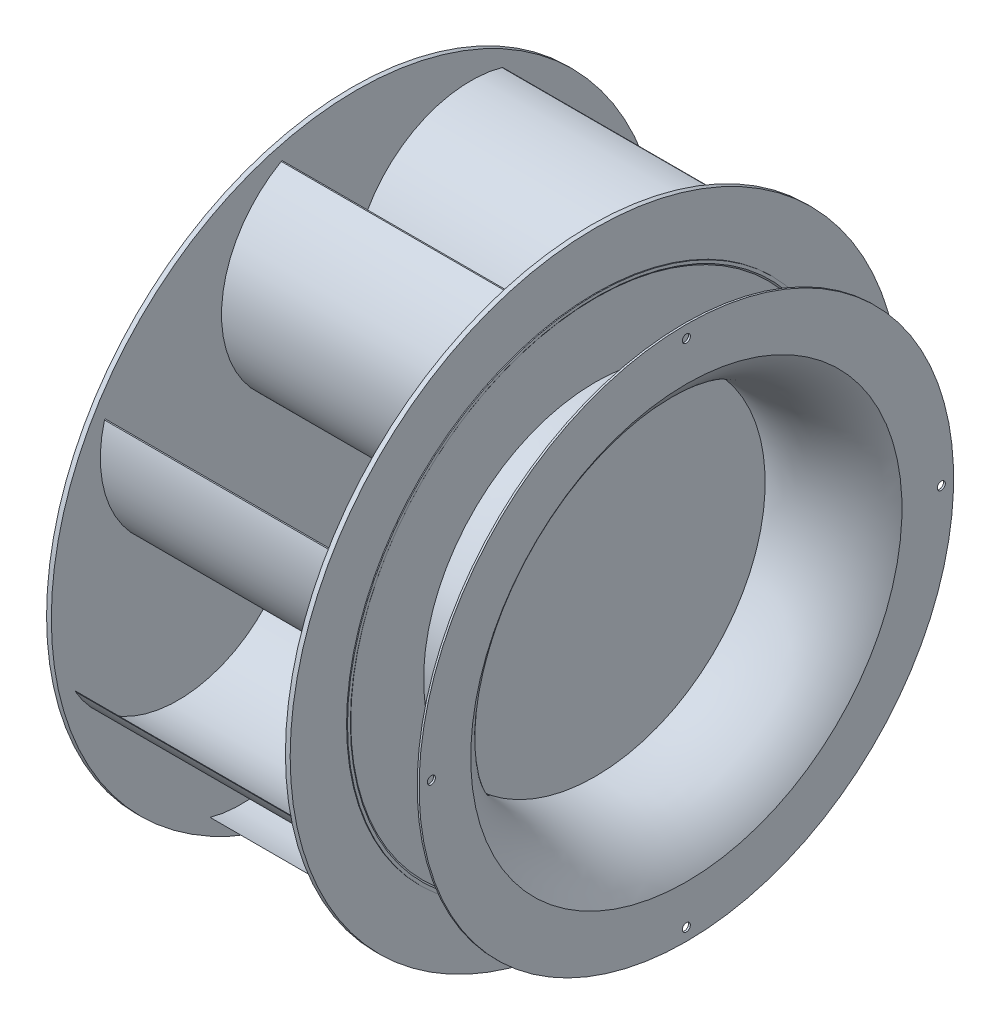
SolidWorks part; units mm, degrees
ref_plane "Front Plane" through (0, 0, 0) normal (0, 0, 1) x (1, 0, 0)
ref_plane "Top Plane" through (0, 0, 0) normal (0, 1, 0) x (1, 0, 0)
ref_plane "Right Plane" through (0, 0, 0) normal (1, 0, 0) x (0, 0, -1)
sketch "Sketch1" plane through (0, 0, 0) normal (0, 0, 1) x (1, 0, 0)
  line L0 (0, 0) -> (831.9083, 0) construction
  line L1 (0, 0) -> (0, 109)
  line L2 (5, 114) -> (70, 114)
  line L3 (70, 114) -> (70, 138)
  line L4 (70, 138) -> (90, 138)
  line L5 (90, 138) -> (90, 98)
  line L6 (90, 98) -> (95, 98)
  line L7 (95, 98) -> (95, 133)
  line L8 (95, 133) -> (105, 133)
  line L9 (105, 133) -> (105, 98)
  line L10 (105, 98) -> (129, 98)
  line L11 (129, 98) -> (129, 0)
  line L12 (129, 0) -> (0, 0)
  arc A0 (5, 114) -> (0, 109) centre (5, 109) ccw
  point P16 (0, 114)
  dimension "D10" = 5
  dimension "D1" = 114
  dimension "D2" = 24
  dimension "D3" = 70
  dimension "D4" = 40
  dimension "D5" = 35
  dimension "D6" = 5
  dimension "D7" = 20
  dimension "D8" = 10
  dimension "D9" = 59
revolve "Revolve1" add sketch "Sketch1" angle 360 about L0
sketch "Sketch2" plane through (129, 0, 0) normal (1, 0, 0) x (0, 0, -1)
  circle A0 centre (0, 0) radius 322
  dimension "D1" = 644
extrude "Extrude1" add sketch "Sketch2" along normal blind 5
sketch "Sketch9" plane through (129, 0, 0) normal (-1, 0, 0) x (0, 0, 1)
  circle A0 centre (0, 0) radius 317
  circle A1 centre (0, 0) radius 100
  circle A2 centre (0, 0) radius 322 construction
  dimension "D1" = 5
  dimension "D2" = 200
extrude "Extrude7" cut sketch "Sketch9" against normal blind 3
ref_plane "Plane1" through (381, 0, 0) normal (1, 0, 0) x (0, 0, -1)
sketch "Sketch3" plane through (381, 0, 0) normal (1, 0, 0) x (0, 0, -1)
  circle A0 centre (0, 0) radius 322
  dimension "D1" = 644
extrude "Extrude2" add sketch "Sketch3" along normal blind 5 separate body
sketch "Sketch4" plane through (134, 0, 0) normal (1, 0, 0) x (0, 0, -1)
  line L0 (0, 0) -> (0, 307) construction
  line L1 (0, 0) -> (161, 278.8602) construction
  line L2 (0, 112.5) -> (0.866, 112)
  line L3 (153.5, 265.8698) -> (154.366, 265.3698)
  circle A0 centre (0, 0) radius 307 construction
  circle A1 centre (0, 0) radius 322 construction
  circle A2 centre (0, 0) radius 112.5 construction
  arc A3 (0, 112.5) -> (153.5, 265.8698) centre (120.6282, 145.2694) cw
  arc A4 (0.866, 112) -> (154.366, 265.3698) centre (121.4942, 144.7694) cw
  dimension "D1" = 15
  dimension "D2" = 225
  dimension "D6" = 125
  dimension "D7" = 125
  dimension "D3" = 30
  dimension "D4" = 60
  dimension "D5" = 1
extrude "Extrude3" add sketch "Sketch4" along normal up to surface (252 mm away) up to face at (386, 0, -322)
ref_axis "Axis1" through (253.5503, 0, 0) along (-1, 0, 0)
pattern_circular "CirPattern1" count 8 over 360 about axis through (253.5503, 0, 0) along (-1, 0, 0) of "Extrude3"
sketch "Sketch5" plane through (0, 0, 0) normal (0, 0, 1) x (1, 0, 0)
  line L0 (0, 0) -> (527.2916, 0) construction
  line L1 (253.5503, 0) -> (75.411, 0) construction
  line L2 (386, 262.5) -> (387, 262.5)
  line L3 (387, 262.5) -> (387, 259.5)
  line L4 (386, 262.5) -> (386, 259.5)
  line L5 (384, 182.5) -> (384, 181.5)
  line L6 (70, 138) -> (70, -138) construction
  line L7 (386, -322) -> (386, 322) construction
  arc A0 (387, 259.5) -> (384, 182.5) centre (443.898, 218.7248) ccw
  arc A1 (386, 259.5) -> (384, 181.5) centre (443.1015, 219.0102) ccw
  dimension "D7" = 70
  dimension "D8" = 70
  dimension "D1" = 181.5
  dimension "D2" = 1
  dimension "D3" = 1
  dimension "D4" = 3
  dimension "D5" = 262.5
  dimension "D6" = 314
revolve "Revolve2" add sketch "Sketch5" angle 360 about L0
ref_plane "Plane3" through (482, 0, 0) normal (1, 0, 0) x (0, 0, -1)
sketch "Sketch6" plane through (0, 0, 0) normal (0, 0, 1) x (1, 0, 0)
  line L0 (482, 282) -> (480, 282)
  line L1 (482, -251.35) -> (482, 251.35) construction
  line L2 (480, 282) -> (480, 227.5)
  line L3 (0, 0) -> (615.1417, 0) construction
  line L4 (0, 114) -> (0, -114) construction
  line L5 (253.5503, 0) -> (75.411, 0) construction
  line L6 (482, 282) -> (482, 227.5)
  line L7 (378, 181.5) -> (382, 181.5)
  line L8 (378, 181.5) -> (378, 179.5)
  line L9 (378, 179.5) -> (382, 179.5)
  arc A0 (382, 181.5) -> (480, 227.5) centre (395.2724, 280.6153) ccw
  arc A1 (382, 179.5) -> (482, 227.5) centre (395.9922, 278.5163) ccw
  dimension "D7" = 100
  dimension "D8" = 100
  dimension "D1" = 282
  dimension "D2" = 2
  dimension "D3" = 227.5
  dimension "D4" = 104
  dimension "D5" = 181.5
  dimension "D6" = 4
revolve "Revolve3" add sketch "Sketch6" angle 360 about L3
sketch "Sketch7" plane through (482, 0, 0) normal (1, 0, 0) x (0, 0, -1)
  line L0 (0, 0) -> (0, 269) construction
  circle A0 centre (0, 0) radius 269 construction
  circle A1 centre (0, 269) radius 4.25
  dimension "D1" = 538
  dimension "D2" = 8.5
extrude "Extrude5" cut sketch "Sketch7" against normal blind 5
pattern_circular "CirPattern2" count 4 over 360 about axis through (253.5503, 0, 0) along (-1, 0, 0) of "Extrude5"
sketch "Sketch8" plane through (0, 0, 0) normal (1, 0, 0) x (0, 0, -1)
  line L0 (0, 0) -> (0, 126) construction
  circle A0 centre (0, 0) radius 126 construction
  circle A1 centre (0, 126) radius 5
  dimension "D1" = 252
  dimension "D2" = 10
extrude "Extrude6" cut sketch "Sketch8" along normal up to surface (90 mm away) up to face at (90, 0, 138)
pattern_circular "CirPattern3" count 8 over 360 about axis through (253.5503, 0, 0) along (-1, 0, 0) of "Extrude6"
